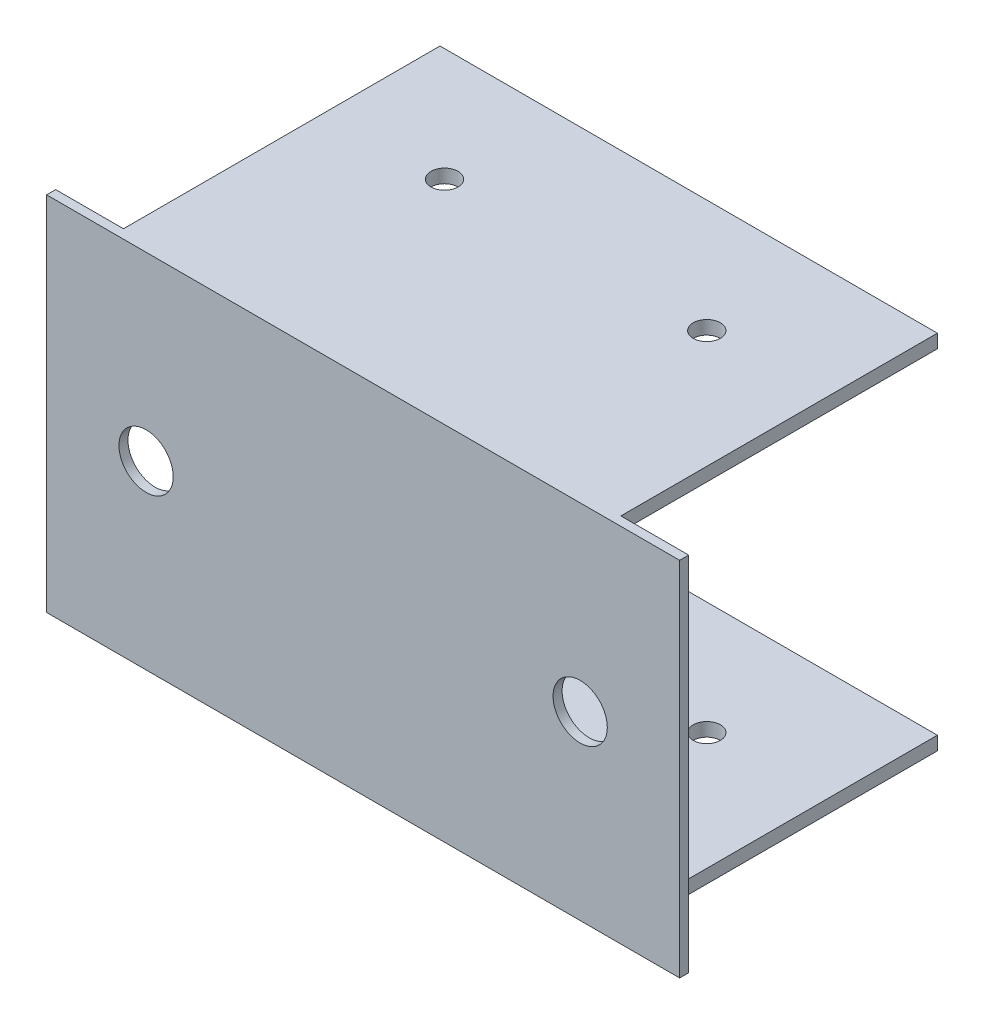
SolidWorks part; units mm, degrees
ref_plane "前视基准面" through (0, 0, 0) normal (0, 0, 1) x (1, 0, 0)
ref_plane "上视基准面" through (0, 0, 0) normal (0, 1, 0) x (1, 0, 0)
ref_plane "右视基准面" through (0, 0, 0) normal (1, 0, 0) x (0, 0, -1)
sketch "草图1" plane through (0, 0, 0) normal (0, 0, 1) x (1, 0, 0)
  line L1 (-35, 20) -> (35, 20)
  line L2 (-35, 20) -> (-35, -20)
  line L3 (-35, -20) -> (35, -20)
  line L4 (35, 20) -> (35, -20)
  line L5 (-35, 20) -> (35, -20) construction
  line L6 (-35, -20) -> (35, 20) construction
  point P0 (0, 0)
  dimension "D1" = 70
  dimension "D2" = 40
extrude "凸台-拉伸1" add sketch "草图1" along normal blind 1 contours L2 L3 L4 L1
sketch "草图2" plane through (0, 0, 1) normal (0, 0, 1) x (1, 0, 0)
  line L0 (-24, 0) -> (24, 0) construction
  circle A0 centre (-24, 0) radius 3
  circle A1 centre (24, 0) radius 3
  point P2 (0, 0)
  dimension "D2" = 6
  dimension "D3" = 6
  dimension "D1" = 48
extrude "切除-拉伸1" cut sketch "草图2" against normal blind 10
sketch "草图4" plane through (0, 20, 0) normal (0, 1, 0) x (1, 0, 0)
  line L0 (-35, -1) -> (35, -1) construction
  line L1 (-27.5, 35) -> (27.5, 35)
  line L2 (-27.5, 35) -> (-27.5, -1)
  line L3 (-27.5, -1) -> (27.5, -1)
  line L4 (27.5, 35) -> (27.5, -1)
  line L5 (-27.5, 35) -> (27.5, -1) construction
  line L6 (-27.5, -1) -> (27.5, 35) construction
  point P0 (0, 17)
  dimension "D1" = 36
  dimension "D2" = 55
extrude "凸台-拉伸2" add sketch "草图4" against normal blind 1.5
extrude "凸台-拉伸3" add sketch "草图4<2>" along normal blind 1.5 from offset 40 offset against normal yes
sketch "草图4<2>" plane through (0, 20, 0) normal (0, 1, 0) x (1, 0, 0) same geometry as "草图4"
sketch "草图5" plane through (0, 20, 0) normal (0, 1, 0) x (1, 0, 0)
  line L0 (-14.5, 22.5) -> (14.5, 22.5) construction
  line L1 (27.5, 35) -> (-27.5, 35) construction
  circle A0 centre (-14.5, 22.5) radius 1.5
  circle A1 centre (14.5, 22.5) radius 1.5
  point P2 (0, 22.5)
  dimension "D3" = 3
  dimension "D4" = 3
  dimension "D1" = 12.5
  dimension "D2" = 29
extrude "切除-拉伸2" cut sketch "草图5" against normal through all
